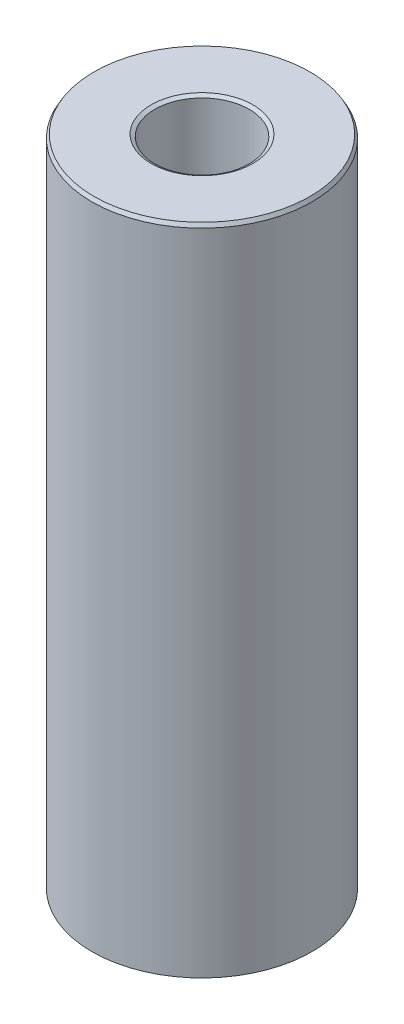
SolidWorks part; units mm, degrees
ref_plane "Front Plane" through (0, 0, 0) normal (0, 0, 1) x (1, 0, 0)
ref_plane "Top Plane" through (0, 0, 0) normal (0, 1, 0) x (1, 0, 0)
ref_plane "Right Plane" through (0, 0, 0) normal (1, 0, 0) x (0, 0, -1)
sketch "Sketch1" plane through (0, 0, 0) normal (0, 1, 0) x (1, 0, 0)
  circle A0 centre (0, 0) radius 52.5
  dimension "SLEEVE_OD" = 105
extrude "Boss-Extrude1" add sketch "Sketch1" along normal blind 312.4604
sketch "Sketch2" plane through (0, 0, 0) normal (0, 1, 0) x (1, 0, 0)
  circle A0 centre (0, 0) radius 22.5508
  dimension "BORE_D" = 45.1016
extrude "Cut-Extrude1" cut sketch "Sketch2" along normal through all
chamfer "Chamfer1" distance 1.7293 angle 30 4 edges at (0, 312.4604, 22.5508) (0, 0, 22.5508) (0, 0, 52.5) (0, 312.4604, 52.5) first distance on face at (0, 312.4604, 22.5508) first distance on face at (0, 0, 22.5508) first distance on face at (0, 312.4604, 52.5)
